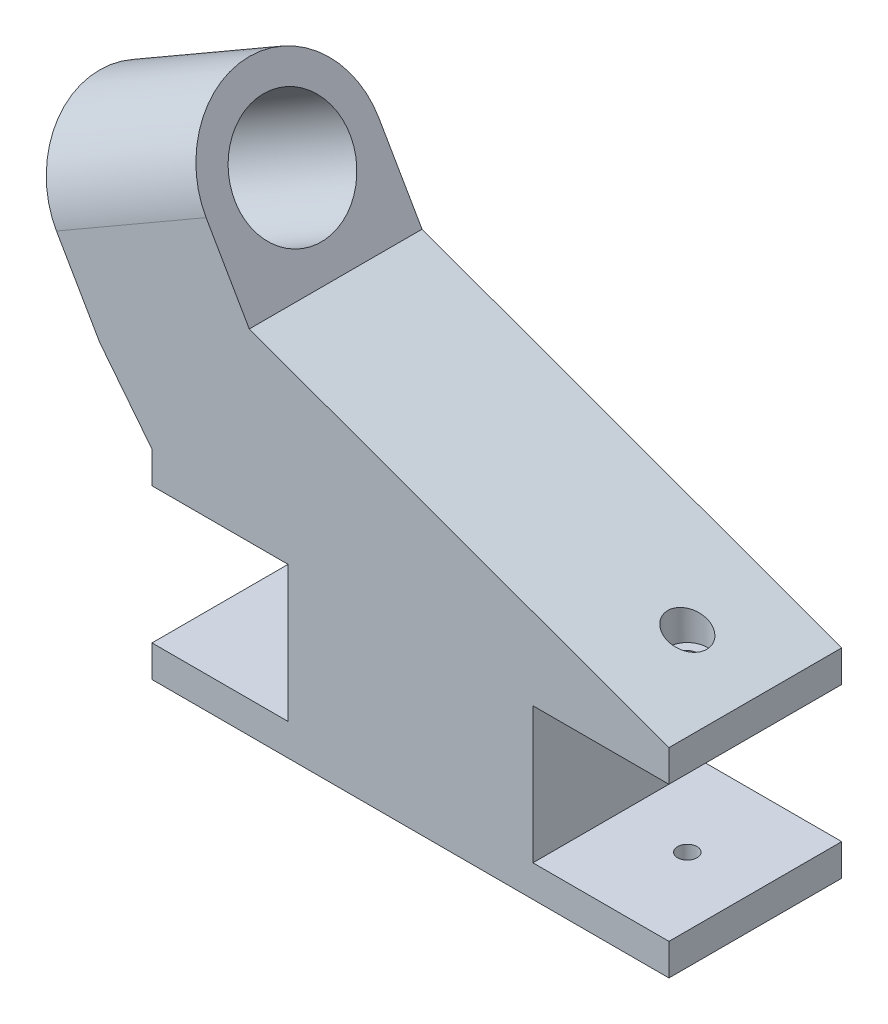
SolidWorks part; units mm, degrees
note: '?' marks a value the reader was unsure of.
ref_plane "Front Plane" through (0, 0, 0) normal (0, 0, 1) x (1, 0, 0)
ref_plane "Top Plane" through (0, 0, 0) normal (0, 1, 0) x (1, 0, 0)
ref_plane "Right Plane" through (0, 0, 0) normal (1, 0, 0) x (0, 0, -1)
sketch "Sketch7" plane through (0, 0, 0) normal (0, 0, 1) x (1, 0, 0)
  line L0 (0, 0) -> (50000, 0) construction
  line L1 (0, 5.5254) -> (0, 50005.5254) construction
  line L7 (-87.5934, 47.625) -> (-54.5978, 66.675)
  line L8 (-54.5978, 66.675) -> (-35.5478, 33.6794)
  line L9 (-68.5434, 14.6294) -> (-35.5478, 33.6794) construction
  line L10 (-46.4007, 49.4106) -> (43254.8695, 25049.4106) construction
  line L20 (57, 0) -> (57, -7)
  line L21 (-54.5978, 66.675) -> (-49.0985, 69.85) construction
  line L22 (-49.0985, 69.85) -> (0, 69.85) construction
  line L23 (57, -7) -> (27, -7)
  line L24 (27, -7) -> (27, -37)
  line L25 (27, -37) -> (57, -37)
  line L26 (57, -37) -> (57, -44)
  line L27 (57, -44) -> (-57, -44)
  line L28 (-57, -44) -> (-57, -37)
  line L29 (-57, -37) -> (-27, -37)
  line L30 (-27, -37) -> (-27, -7)
  line L31 (-27, -7) -> (-57, -7)
  line L40 (-35.5478, 33.6794) -> (57, 0)
  line L41 (-87.5934, 47.625) -> (-68.5434, 14.6294)
  line L43 (-57, -7) -> (-57, 0)
  line L44 (-57, 0) -> (-68.5434, 14.6294)
  point P2 (0, -44)
  point P7 (0, 76.2)
  point P16 (-45.0728, 50.1772)
  dimension "D2" = 38.1
  dimension "D4" = 6.35
  dimension "D9" = 6.35
  dimension "D3" = 30
  dimension "D5" = 54
  dimension "D6" = 7
  dimension "D1" = 30
  dimension "D7" = 76.2
  dimension "D8" = 38.1
extrude "Boss-Extrude1" add sketch "Sketch7" along normal blind 38.1 contours L7 L8 L40 L20 L23 L24 L25 L26 L27 L28 L29 L30 L31 L43 L44 L41
sketch "Sketch8" plane through (-12.0772, -6.9728, 0) normal (0.866, 0.5, 0) x (0, 0, -1)
  line L0 (0, 85.0411) -> (0, 46.9411) construction
  line L1 (-38.1, 85.0411) -> (-38.1, 46.9411) construction
  line L2 (-38.1, 85.0411) -> (0, 85.0411) construction
  line L3 (0, 85.0411) -> (0, 46.9411)
  line L4 (-38.1, 85.0411) -> (-38.1, 46.9411)
  line L5 (-38.1, 85.0411) -> (0, 85.0411)
  arc A0 (-38.1, 65.9911) -> (0, 65.9911) centre (-19.05, 65.9911) cw
extrude "Cut-Extrude1" cut sketch "Sketch8" against normal through all
sketch "Sketch15" plane through (-12.0772, -6.9728, 0) normal (0.866, 0.5, 0) x (0, 0, -1)
  line L0 (-38.1, 65.9911) -> (0, 65.9911) construction
  point P0 (-19.05, 65.9911)
hole_wizard "Hole3" positions "Sketch15" profile "Sketch16" legacy end condition through all
sketch "Sketch16" plane through (-45.0728, 50.1772, 19.05) normal (0, 0, 1) x (-0.5, 0.866, 0)
  line L0 (0, 0) -> (0, 83.9125)
  line L1 (0, 83.9125) -> (12.7, 83.9125)
  line L2 (12.7, 83.9125) -> (12.7, 0)
  line L3 (12.7, 0) -> (0, 0)
  line L4 (0, 110) -> (0, -10) construction
  dimension "Depth" = 83.9125
sketch "Sketch17" plane through (0, -44, 0) normal (0, -1, 0) x (1, 0, 0)
  line L0 (27, 0) -> (57, 0) construction
  line L1 (57, 38.1) -> (57, 0) construction
  line L2 (27, 38.1) -> (57, 38.1) construction
  line L3 (-57, 38.1) -> (-57, 0) construction
  line L4 (-57, 0) -> (-27, 0) construction
  line L5 (-57, 38.1) -> (-27, 38.1) construction
  line L6 (27, 0) -> (57, 0) construction
  line L7 (57, 38.1) -> (57, 0) construction
  line L8 (27, 38.1) -> (57, 38.1) construction
  line L9 (-57, 38.1) -> (-57, 0) construction
  line L10 (-57, 0) -> (-27, 0) construction
  line L11 (-57, 38.1) -> (-27, 38.1) construction
  line L12 (42, 38.1) -> (42, 0) construction
  line L13 (-42, 38.1) -> (-42, 0) construction
  line L14 (57, 19.05) -> (-57, 19.05) construction
  point P14 (42, 19.05)
  point P15 (-42, 19.05)
hole_wizard "Hole4" positions "Sketch17" profile "Sketch18" legacy end condition up to next
sketch "Sketch18" plane through (-42, -44, 19.05) normal (1, 0, 0) x (0, 0, -1)
  line L0 (0, 0) -> (0, 7)
  line L1 (0, 7) -> (2.15, 7)
  line L2 (2.15, 7) -> (2.15, 0)
  line L3 (2.15, 0) -> (0, 0)
  line L4 (0, 110) -> (0, -10) construction
  dimension "Diameter" = 4.3
  dimension "Depth" = 7
sketch "Sketch20" plane through (0, -7, 0) normal (0, -1, 0) x (1, 0, 0)
  line L0 (27, 19.05) -> (57, 19.05) construction
  line L1 (42, 38.1) -> (42, 0) construction
  line L4 (27, 0) -> (57, 0)
  line L5 (57, 0) -> (57, 38.1)
  line L6 (57, 38.1) -> (27, 38.1)
  line L7 (27, 38.1) -> (27, 0)
  line L8 (27, 0) -> (57, 0) construction
  line L9 (57, 0) -> (57, 38.1) construction
  line L10 (57, 38.1) -> (27, 38.1) construction
  line L11 (27, 38.1) -> (27, 0) construction
  point P8 (42, 19.05)
  dimension "D1" = 0
hole_wizard "Hole5" positions "Sketch20" profile "Sketch21" legacy end condition through all
sketch "Sketch21" plane through (42, -7, 19.05) normal (1, 0, 0) x (0, 0, -1)
  line L0 (0, 0) -> (0, 73.675)
  line L1 (0, 73.675) -> (4.3, 73.675)
  line L2 (4.3, 73.675) -> (4.3, 7)
  line L3 (4.3, 7) -> (2.15, 7)
  line L4 (2.15, 7) -> (2.15, 0)
  line L5 (2.15, 0) -> (0, 0)
  line L6 (0, 110) -> (0, -10) construction
  dimension "Diameter" = 8.6
  dimension "Depth" = 73.675
  dimension "C-Bore Diameter" = 4.3
  dimension "C-Bore Depth" = 7
sketch "Sketch23" plane through (0, 0, 0) normal (1, 0, 0) x (0, 0, -1)
  line L1 (57.15, 0) -> (57.15, 50000) construction
  ellipse E0 centre (-19.05, 50.1772) end of major axis (-6.35, 50.1772) minor radius 10.9985 construction
  ellipse E1 centre (-19.05, 50.1772) end of major axis (-6.35, 50.1772) minor radius 10.9985 construction
ref_axis "Axis5" through (0, 14.4472, -57.15) along (0, 1, 0)?
equation "\"OD\"= 1"
equation "\"nozzle_angle\"= 30"
equation "\"l_flange\"= 0.25"
equation "\"l_mount\"= 1.5"
equation "\"w_int\"= 30mm"
equation "\"t_base\"= 7mm"
equation "\"D1@Boss-Extrude1\"=\"d_flange\""
equation "\"Diameter@Sketch16\"=\"OD\""
equation "\"d_mount_hole\"= 4.3mm"
equation "\"d_mount_hole_clearance\"= \"d_mount_hole\" * 2"
equation "\"d_flange\"= 1.5"
equation "\"D2@Sketch7\"=\"d_flange\""
equation "\"D4@Sketch7\"=\"l_flange\""
equation "\"turb_dist\"= .25"
equation "\"D9@Sketch7\"=\"turb_dist\""
equation "\"D3@Sketch7\"=\"w_int\""
equation "\"d_bearing\"= 40mm"
equation "\"D5@Sketch7\"=\"d_bearing\"+\"t_base\"*2"
equation "\"D6@Sketch7\"=\"t_base\""
equation "\"Diameter@Sketch18\"=\"d_mount_hole\""
equation "\"C-Bore Depth@Sketch21\"=\"t_base\""
equation "\"C-Bore Diameter@Sketch21\"=\"d_mount_hole\""
equation "\"Diameter@Sketch21\"=\"d_mount_hole_clearance\""
equation "\"h_center\"= 3"
equation "\"D7@Sketch7\"=\"h_center\""
equation "\"D8@Sketch7\"=\"l_mount\""
equation "\"D1@Sketch7\"=\"nozzle_angle\""
equation "\"cent_dist\"= 3"
equation "\"D1@Sketch23\"=\"cent_dist\""
